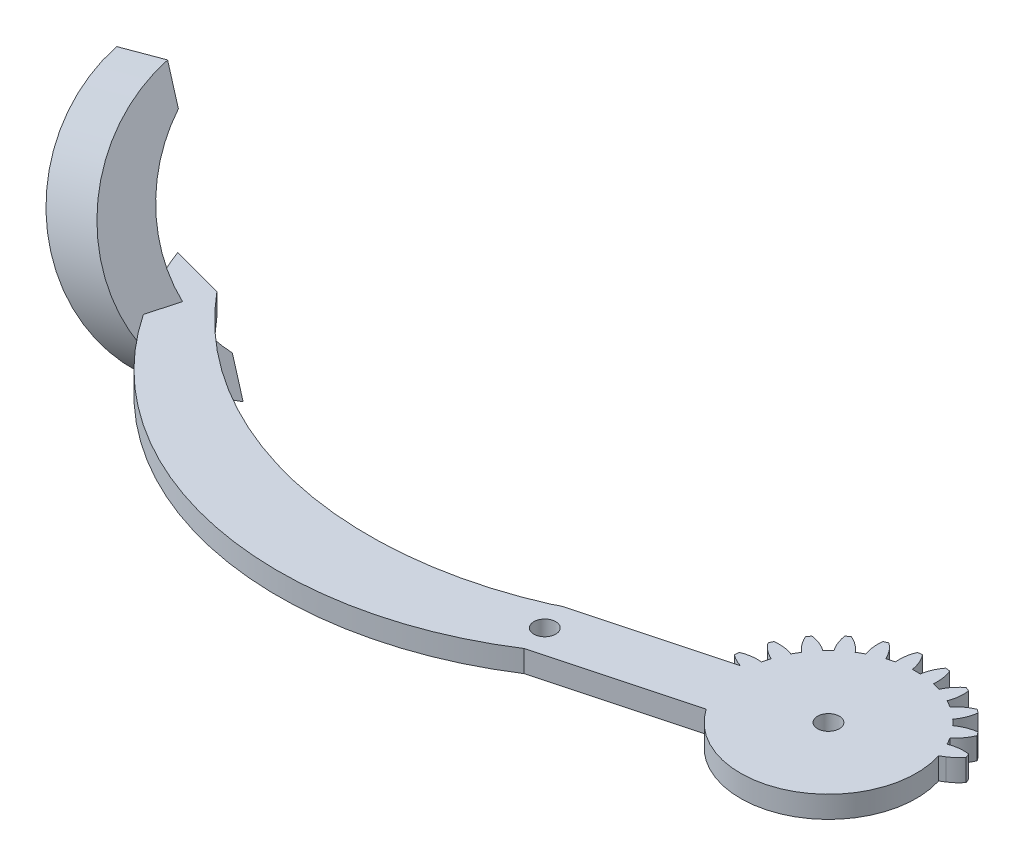
SolidWorks part; units mm, degrees
ref_plane "Front Plane" through (0, 0, 0) normal (0, 0, 1) x (1, 0, 0)
ref_plane "Top Plane" through (0, 0, 0) normal (0, 1, 0) x (1, 0, 0)
ref_plane "Right Plane" through (0, 0, 0) normal (1, 0, 0) x (0, 0, -1)
sketch "Sketch1" plane through (0, 0, 0) normal (0, 1, 0) x (1, 0, 0)
  line L0 (20.6437, 4) -> (2.0816, 4)
  line L1 (2.0816, -4) -> (20.6437, -4)
  arc A0 (2.0816, 4) -> (3.5217, 5.3071) centre (-0.7683, 8.5867) ccw
  arc A1 (3.5217, 5.3071) -> (3.2829, 5.8838) centre (-10.1063, 0) ccw
  arc A2 (3.2829, 5.8838) -> (0.6271, 5.5703) centre (2.5684, 0.5313) ccw
  arc A3 (0.6271, 5.5703) -> (0.0844, 6.5103) centre (-10.1063, 0) ccw
  arc A4 (0.0844, 6.5103) -> (1.6838, 8.6535) centre (-3.3089, 10.711) ccw
  arc A5 (1.6838, 8.6535) -> (1.3038, 9.1487) centre (-10.1063, 0) ccw
  arc A6 (1.3038, 9.1487) -> (-1.1803, 8.1585) centre (1.999, 3.7936) ccw
  arc A7 (-1.1803, 8.1585) -> (-1.9479, 8.926) centre (-10.1063, 0) ccw
  arc A8 (-1.9479, 8.926) -> (-0.9576, 11.4102) centre (-6.3127, 12.1053) ccw
  arc A9 (-0.9576, 11.4102) -> (-1.4528, 11.7901) centre (-10.1063, 0) ccw
  arc A10 (-1.4528, 11.7901) -> (-3.596, 10.1907) centre (0.6046, 6.7975) ccw
  arc A11 (-3.596, 10.1907) -> (-4.5361, 10.7334) centre (-10.1063, 0) ccw
  arc A12 (-4.5361, 10.7334) -> (-4.2225, 13.3892) centre (-9.5751, 12.6747) ccw
  arc A13 (-4.2225, 13.3892) -> (-4.7992, 13.6281) centre (-10.1063, 0) ccw
  arc A14 (-4.7992, 13.6281) -> (-6.4554, 11.5285) centre (-1.5196, 9.3381) ccw
  arc A15 (-6.4554, 11.5285) -> (-7.5039, 11.8094) centre (-10.1063, 0) ccw
  arc A16 (-7.5039, 11.8094) -> (-7.8884, 14.4558) centre (-12.8736, 12.3803) ccw
  arc A17 (-7.8884, 14.4558) -> (-8.5072, 14.5373) centre (-10.1063, 0) ccw
  arc A18 (-8.5072, 14.5373) -> (-9.5636, 12.0806) centre (-4.2291, 11.2423) ccw
  arc A19 (-9.5636, 12.0806) -> (-10.6491, 12.0806) centre (-10.1063, 0) ccw
  arc A20 (-10.6491, 12.0806) -> (-11.7054, 14.5373) centre (-15.9836, 11.2423) ccw
  arc A21 (-11.7054, 14.5373) -> (-12.3243, 14.4558) centre (-10.1063, 0) ccw
  arc A22 (-12.3243, 14.4558) -> (-12.7088, 11.8094) centre (-7.3391, 12.3803) ccw
  arc A23 (-12.7088, 11.8094) -> (-13.7573, 11.5285) centre (-10.1063, 0) ccw
  arc A24 (-13.7573, 11.5285) -> (-15.4135, 13.6281) centre (-18.6931, 9.3381) ccw
  arc A25 (-15.4135, 13.6281) -> (-15.9901, 13.3892) centre (-10.1063, 0) ccw
  arc A26 (-15.9901, 13.3892) -> (-15.6766, 10.7334) centre (-10.6376, 12.6747) ccw
  arc A27 (-15.6766, 10.7334) -> (-16.6166, 10.1907) centre (-10.1063, 0) ccw
  arc A28 (-16.6166, 10.1907) -> (-18.7599, 11.7901) centre (-20.8173, 6.7975) ccw
  arc A29 (-18.7599, 11.7901) -> (-19.255, 11.4102) centre (-10.1063, 0) ccw
  arc A30 (-19.255, 11.4102) -> (-18.2648, 8.926) centre (-13.9, 12.1053) ccw
  arc A31 (-18.2648, 8.926) -> (-19.0324, 8.1585) centre (-10.1063, 0) ccw
  arc A32 (-19.0324, 8.1585) -> (-21.5165, 9.1487) centre (-22.2117, 3.7936) ccw
  arc A33 (-21.5165, 9.1487) -> (-21.8965, 8.6535) centre (-10.1063, 0) ccw
  arc A34 (-21.8965, 8.6535) -> (-20.2971, 6.5103) centre (-16.9038, 10.711) ccw
  arc A35 (-20.2971, 6.5103) -> (-20.8398, 5.5703) centre (-10.1063, 0) ccw
  arc A36 (-20.8398, 5.5703) -> (-23.4956, 5.8838) centre (-22.7811, 0.5313) ccw
  arc A37 (-23.4956, 5.8838) -> (-23.7344, 5.3071) centre (-10.1063, 0) ccw
  arc A38 (-23.7344, 5.3071) -> (-21.6348, 3.6509) centre (-19.4444, 8.5867) ccw
  arc A39 (-21.6348, 3.6509) -> (-21.9157, 2.6025) centre (-10.1063, 0) ccw
  arc A40 (-21.9157, 2.6025) -> (-24.5622, 2.2179) centre (-22.4867, -2.7673) ccw
  arc A41 (-24.5622, 2.2179) -> (-24.6437, 1.5991) centre (-10.1063, 0) ccw
  arc A42 (-24.6437, 1.5991) -> (-22.1869, 0.5427) centre (-21.3486, 5.8773) ccw
  arc A43 (-22.1869, 0.5427) -> (-22.1869, -0.5427) centre (-10.1063, 0) ccw
  arc A44 (-22.1869, -0.5427) -> (-24.6437, -1.5991) centre (-21.3486, -5.8773) ccw
  arc A45 (-24.6437, -1.5991) -> (-24.5622, -2.2179) centre (-10.1063, 0) ccw
  arc A46 (-24.5622, -2.2179) -> (-21.9157, -2.6025) centre (-22.4867, 2.7673) ccw
  arc A47 (-21.9157, -2.6025) -> (-21.6348, -3.6509) centre (-10.1063, 0) ccw
  arc A48 (-21.6348, -3.6509) -> (-23.7344, -5.3071) centre (-19.4444, -8.5867) ccw
  arc A49 (-23.7344, -5.3071) -> (-23.4956, -5.8838) centre (-10.1063, 0) ccw
  arc A50 (-23.4956, -5.8838) -> (-20.8398, -5.5703) centre (-22.7811, -0.5313) ccw
  arc A51 (-20.8398, -5.5703) -> (-20.2971, -6.5103) centre (-10.1063, 0) ccw
  arc A52 (-20.2971, -6.5103) -> (-21.8965, -8.6535) centre (-16.9038, -10.711) ccw
  arc A53 (-21.8965, -8.6535) -> (-21.5165, -9.1487) centre (-10.1063, 0) ccw
  arc A54 (-21.5165, -9.1487) -> (-19.0324, -8.1585) centre (-22.2117, -3.7936) ccw
  arc A55 (-19.0324, -8.1585) -> (-18.2648, -8.926) centre (-10.1063, 0) ccw
  arc A56 (-18.2648, -8.926) -> (-19.255, -11.4102) centre (-13.9, -12.1053) ccw
  arc A57 (-19.255, -11.4102) -> (-18.7599, -11.7901) centre (-10.1063, 0) ccw
  arc A58 (-18.7599, -11.7901) -> (-16.6166, -10.1907) centre (-20.8173, -6.7975) ccw
  arc A59 (-16.6166, -10.1907) -> (-15.6766, -10.7334) centre (-10.1063, 0) ccw
  arc A60 (-15.6766, -10.7334) -> (-15.9901, -13.3892) centre (-10.6376, -12.6747) ccw
  arc A61 (-15.9901, -13.3892) -> (-15.4135, -13.6281) centre (-10.1063, 0) ccw
  arc A62 (-15.4135, -13.6281) -> (-13.7573, -11.5285) centre (-18.6931, -9.3381) ccw
  arc A63 (-13.7573, -11.5285) -> (-12.7088, -11.8094) centre (-10.1063, 0) ccw
  arc A64 (-12.7088, -11.8094) -> (-12.3243, -14.4558) centre (-7.3391, -12.3803) ccw
  arc A65 (-12.3243, -14.4558) -> (-11.7054, -14.5373) centre (-10.1063, 0) ccw
  arc A66 (-11.7054, -14.5373) -> (-10.6491, -12.0806) centre (-15.9836, -11.2423) ccw
  arc A67 (-10.6491, -12.0806) -> (-9.5636, -12.0806) centre (-10.1063, 0) ccw
  arc A68 (-9.5636, -12.0806) -> (-8.5072, -14.5373) centre (-4.2291, -11.2423) ccw
  arc A69 (-8.5072, -14.5373) -> (-7.8884, -14.4558) centre (-10.1063, 0) ccw
  arc A70 (-7.8884, -14.4558) -> (-7.5039, -11.8094) centre (-12.8736, -12.3803) ccw
  arc A71 (-7.5039, -11.8094) -> (-6.4554, -11.5285) centre (-10.1063, 0) ccw
  arc A72 (-6.4554, -11.5285) -> (-4.7992, -13.6281) centre (-1.5196, -9.3381) ccw
  arc A73 (-4.7992, -13.6281) -> (-4.2225, -13.3892) centre (-10.1063, 0) ccw
  arc A74 (-4.2225, -13.3892) -> (-4.5361, -10.7334) centre (-9.5751, -12.6747) ccw
  arc A75 (-4.5361, -10.7334) -> (-3.596, -10.1907) centre (-10.1063, 0) ccw
  arc A76 (-3.596, -10.1907) -> (-1.4528, -11.7901) centre (0.6046, -6.7975) ccw
  arc A77 (-1.4528, -11.7901) -> (-0.9576, -11.4102) centre (-10.1063, 0) ccw
  arc A78 (-0.9576, -11.4102) -> (-1.9479, -8.926) centre (-6.3127, -12.1053) ccw
  arc A79 (-1.9479, -8.926) -> (-1.1803, -8.1585) centre (-10.1063, 0) ccw
  arc A80 (-1.1803, -8.1585) -> (1.3038, -9.1487) centre (1.999, -3.7936) ccw
  arc A81 (1.3038, -9.1487) -> (1.6838, -8.6535) centre (-10.1063, 0) ccw
  arc A82 (1.6838, -8.6535) -> (0.0844, -6.5103) centre (-3.3089, -10.711) ccw
  arc A83 (0.0844, -6.5103) -> (0.6271, -5.5703) centre (-10.1063, 0) ccw
  arc A84 (0.6271, -5.5703) -> (3.2829, -5.8838) centre (2.5684, -0.5313) ccw
  arc A85 (3.2829, -5.8838) -> (3.5217, -5.3071) centre (-10.1063, 0) ccw
  arc A86 (3.5217, -5.3071) -> (2.0816, -4) centre (-0.7683, -8.5867) ccw
  arc A87 (20.6437, -4) -> (20.6437, 4) centre (20.6437, 0) ccw
  circle A88 centre (-10.1063, 0) radius 1.5
  circle A89 centre (20.6437, 0) radius 1.5
  dimension "D1" = 3
  dimension "D2" = 3
extrude "Boss-Extrude1" add sketch "Sketch1" along normal blind 3
sketch "Sketch3" plane through (0, 3, 0) normal (0, 1, 0) x (1, 0, 0)
  line L0 (-10.1063, 0) -> (-40.8563, 0) construction
  line L1 (-10.1063, 0) -> (-40.8563, -8.2394)
  line L2 (-11.1416, 3.8637) -> (-41.8916, -4.3757)
  line L3 (-9.0711, -3.8637) -> (-39.8211, -12.1031)
  circle A0 centre (-10.1063, 0) radius 1.5
  circle A1 centre (20.6437, 0) radius 1.5 construction
  circle A2 centre (20.6437, 0) radius 1.5
  circle A3 centre (-40.8563, -8.2394) radius 1.5
  circle A4 centre (-40.8563, -8.2394) radius 4
  circle A5 centre (-10.1063, 0) radius 4
  dimension "D2" = 3
  dimension "D5" = 3
  dimension "D6" = 8
  dimension "D7" = 8
  dimension "D1" = 30.75
  dimension "D3" = 30.75
  dimension "D4" = 15
extrude "Boss-Extrude2" add sketch "Sketch3" against normal blind 3 contours L0 A5 L2 | A5 L0 L2 A4 L1 | A4 A3 | A5 L1 A4 L3 | L0 A0 L1 A5 | A0 L0 A5 L1 region at (-13.0123, 3, 0.3826) region at (-12.8563, 3, -0.1131) region at (-28.0097, 3, 2.8847) region at (-17.5095, 3, -1.168) region at (-24.9445, 3, 6.1234) region at (-37.0027, 3, 7.7321)
sketch "Sketch4" plane through (0, 3, 0) normal (0, 1, 0) x (1, 0, 0)
  line L0 (20.6437, 4) -> (2.0816, 4) construction
  line L1 (2.0816, -4) -> (20.6437, -4) construction
  line L2 (20.6437, 4) -> (2.0816, 4)
  line L3 (2.0816, -4) -> (20.6437, -4)
  line L4 (2.0816, 4) -> (1.4381, 3.6001)
  line L5 (-20.8438, -7.0182) -> (-20.0942, -6.8174)
  line L8 (-22.9143, 0.7092) -> (-41.8916, -4.3757)
  line L9 (-39.8211, -12.1031) -> (-20.8438, -7.0182)
  line L10 (2.0816, -4) -> (20.6437, -4)
  line L11 (20.6437, 4) -> (2.0816, 4)
  line L12 (-22.9143, 0.7092) -> (-41.8916, -4.3757)
  line L13 (-39.8211, -12.1031) -> (-20.8438, -7.0182)
  line L14 (2.0816, -4) -> (20.6437, -4)
  line L15 (20.6437, 4) -> (2.0816, 4)
  circle A0 centre (-10.1063, 0) radius 12.0927
  arc A1 (3.2829, 5.8838) -> (0.6271, 5.5703) centre (2.5684, 0.5313) ccw construction
  arc A2 (3.5217, 5.3071) -> (3.2829, 5.8838) centre (-10.1063, 0) ccw construction
  arc A3 (2.0816, 4) -> (3.5217, 5.3071) centre (-0.7683, 8.5867) ccw construction
  arc A4 (20.6437, -4) -> (20.6437, 4) centre (20.6437, 0) ccw construction
  arc A5 (3.5217, -5.3071) -> (2.0816, -4) centre (-0.7683, -8.5867) ccw construction
  arc A6 (3.2829, -5.8838) -> (3.5217, -5.3071) centre (-10.1063, 0) ccw construction
  arc A7 (0.6271, -5.5703) -> (3.2829, -5.8838) centre (2.5684, -0.5313) ccw construction
  arc A8 (3.2829, 5.8838) -> (0.6271, 5.5703) centre (2.5684, 0.5313) ccw
  arc A9 (3.5217, 5.3071) -> (3.2829, 5.8838) centre (-10.1063, 0) ccw
  arc A10 (2.0816, 4) -> (3.5217, 5.3071) centre (-0.7683, 8.5867) ccw
  arc A11 (20.6437, -4) -> (20.6437, 4) centre (20.6437, 0) ccw
  arc A12 (3.5217, -5.3071) -> (2.0816, -4) centre (-0.7683, -8.5867) ccw
  arc A13 (3.2829, -5.8838) -> (3.5217, -5.3071) centre (-10.1063, 0) ccw
  arc A14 (0.6271, -5.5703) -> (3.2829, -5.8838) centre (2.5684, -0.5313) ccw
  arc A95 (-24.6437, 1.5991) -> (-22.9143, 0.7092) centre (-21.3486, 5.8773) ccw
  arc A96 (-41.8916, -4.3757) -> (-39.8211, -12.1031) centre (-40.8563, -8.2394) ccw
  arc A97 (-20.8438, -7.0182) -> (-21.8965, -8.6535) centre (-16.9038, -10.711) ccw
  arc A98 (-21.8965, -8.6535) -> (-21.5165, -9.1487) centre (-10.1063, 0) ccw
  arc A99 (-21.5165, -9.1487) -> (-19.0324, -8.1585) centre (-22.2117, -3.7936) ccw
  arc A100 (-19.0324, -8.1585) -> (-18.2648, -8.926) centre (-10.1063, 0) ccw
  arc A101 (-18.2648, -8.926) -> (-19.255, -11.4102) centre (-13.9, -12.1053) ccw
  arc A102 (-19.255, -11.4102) -> (-18.7599, -11.7901) centre (-10.1063, 0) ccw
  arc A103 (-18.7599, -11.7901) -> (-16.6166, -10.1907) centre (-20.8173, -6.7975) ccw
  arc A104 (-16.6166, -10.1907) -> (-15.6766, -10.7334) centre (-10.1063, 0) ccw
  arc A105 (-15.6766, -10.7334) -> (-15.9901, -13.3892) centre (-10.6376, -12.6747) ccw
  arc A106 (-15.9901, -13.3892) -> (-15.4135, -13.6281) centre (-10.1063, 0) ccw
  arc A107 (-15.4135, -13.6281) -> (-13.7573, -11.5285) centre (-18.6931, -9.3381) ccw
  arc A108 (-13.7573, -11.5285) -> (-12.7088, -11.8094) centre (-10.1063, 0) ccw
  arc A109 (-12.7088, -11.8094) -> (-12.3243, -14.4558) centre (-7.3391, -12.3803) ccw
  arc A110 (-12.3243, -14.4558) -> (-11.7054, -14.5373) centre (-10.1063, 0) ccw
  arc A111 (-11.7054, -14.5373) -> (-10.6491, -12.0806) centre (-15.9836, -11.2423) ccw
  arc A112 (-10.6491, -12.0806) -> (-9.5636, -12.0806) centre (-10.1063, 0) ccw
  arc A113 (-9.5636, -12.0806) -> (-8.5072, -14.5373) centre (-4.2291, -11.2423) ccw
  arc A114 (-8.5072, -14.5373) -> (-7.8884, -14.4558) centre (-10.1063, 0) ccw
  arc A115 (-7.8884, -14.4558) -> (-7.5039, -11.8094) centre (-12.8736, -12.3803) ccw
  arc A116 (-7.5039, -11.8094) -> (-6.4554, -11.5285) centre (-10.1063, 0) ccw
  arc A117 (-6.4554, -11.5285) -> (-4.7992, -13.6281) centre (-1.5196, -9.3381) ccw
  arc A118 (-4.7992, -13.6281) -> (-4.2225, -13.3892) centre (-10.1063, 0) ccw
  arc A119 (-4.2225, -13.3892) -> (-4.5361, -10.7334) centre (-9.5751, -12.6747) ccw
  arc A120 (-4.5361, -10.7334) -> (-3.596, -10.1907) centre (-10.1063, 0) ccw
  arc A121 (-3.596, -10.1907) -> (-1.4528, -11.7901) centre (0.6046, -6.7975) ccw
  arc A122 (-1.4528, -11.7901) -> (-0.9576, -11.4102) centre (-10.1063, 0) ccw
  arc A123 (-0.9576, -11.4102) -> (-1.9479, -8.926) centre (-6.3127, -12.1053) ccw
  arc A124 (-1.9479, -8.926) -> (-1.1803, -8.1585) centre (-10.1063, 0) ccw
  arc A125 (-1.1803, -8.1585) -> (1.3038, -9.1487) centre (1.999, -3.7936) ccw
  arc A126 (1.3038, -9.1487) -> (1.6838, -8.6535) centre (-10.1063, 0) ccw
  arc A127 (1.6838, -8.6535) -> (0.0844, -6.5103) centre (-3.3089, -10.711) ccw
  arc A128 (0.0844, -6.5103) -> (0.6271, -5.5703) centre (-10.1063, 0) ccw
  arc A129 (0.6271, -5.5703) -> (3.2829, -5.8838) centre (2.5684, -0.5313) ccw
  arc A130 (3.2829, -5.8838) -> (3.5217, -5.3071) centre (-10.1063, 0) ccw
  arc A131 (3.5217, -5.3071) -> (2.0816, -4) centre (-0.7683, -8.5867) ccw
  arc A132 (20.6437, -4) -> (20.6437, 4) centre (20.6437, 0) ccw
  arc A133 (2.0816, 4) -> (3.5217, 5.3071) centre (-0.7683, 8.5867) ccw
  arc A134 (3.5217, 5.3071) -> (3.2829, 5.8838) centre (-10.1063, 0) ccw
  arc A135 (3.2829, 5.8838) -> (0.6271, 5.5703) centre (2.5684, 0.5313) ccw
  arc A136 (0.6271, 5.5703) -> (0.0844, 6.5103) centre (-10.1063, 0) ccw
  arc A137 (0.0844, 6.5103) -> (1.6838, 8.6535) centre (-3.3089, 10.711) ccw
  arc A138 (1.6838, 8.6535) -> (1.3038, 9.1487) centre (-10.1063, 0) ccw
  arc A139 (1.3038, 9.1487) -> (-1.1803, 8.1585) centre (1.999, 3.7936) ccw
  arc A140 (-1.1803, 8.1585) -> (-1.9479, 8.926) centre (-10.1063, 0) ccw
  arc A141 (-1.9479, 8.926) -> (-0.9576, 11.4102) centre (-6.3127, 12.1053) ccw
  arc A142 (-0.9576, 11.4102) -> (-1.4528, 11.7901) centre (-10.1063, 0) ccw
  arc A143 (-1.4528, 11.7901) -> (-3.596, 10.1907) centre (0.6046, 6.7975) ccw
  arc A144 (-3.596, 10.1907) -> (-4.5361, 10.7334) centre (-10.1063, 0) ccw
  arc A145 (-4.5361, 10.7334) -> (-4.2225, 13.3892) centre (-9.5751, 12.6747) ccw
  arc A146 (-4.2225, 13.3892) -> (-4.7992, 13.6281) centre (-10.1063, 0) ccw
  arc A147 (-4.7992, 13.6281) -> (-6.4554, 11.5285) centre (-1.5196, 9.3381) ccw
  arc A148 (-6.4554, 11.5285) -> (-7.5039, 11.8094) centre (-10.1063, 0) ccw
  arc A149 (-7.5039, 11.8094) -> (-7.8884, 14.4558) centre (-12.8736, 12.3803) ccw
  arc A150 (-7.8884, 14.4558) -> (-8.5072, 14.5373) centre (-10.1063, 0) ccw
  arc A151 (-8.5072, 14.5373) -> (-9.5636, 12.0806) centre (-4.2291, 11.2423) ccw
  arc A152 (-9.5636, 12.0806) -> (-10.6491, 12.0806) centre (-10.1063, 0) ccw
  arc A153 (-10.6491, 12.0806) -> (-11.7054, 14.5373) centre (-15.9836, 11.2423) ccw
  arc A154 (-11.7054, 14.5373) -> (-12.3243, 14.4558) centre (-10.1063, 0) ccw
  arc A155 (-12.3243, 14.4558) -> (-12.7088, 11.8094) centre (-7.3391, 12.3803) ccw
  arc A156 (-12.7088, 11.8094) -> (-13.7573, 11.5285) centre (-10.1063, 0) ccw
  arc A157 (-13.7573, 11.5285) -> (-15.4135, 13.6281) centre (-18.6931, 9.3381) ccw
  arc A158 (-15.4135, 13.6281) -> (-15.9901, 13.3892) centre (-10.1063, 0) ccw
  arc A159 (-15.9901, 13.3892) -> (-15.6766, 10.7334) centre (-10.6376, 12.6747) ccw
  arc A160 (-15.6766, 10.7334) -> (-16.6166, 10.1907) centre (-10.1063, 0) ccw
  arc A161 (-16.6166, 10.1907) -> (-18.7599, 11.7901) centre (-20.8173, 6.7975) ccw
  arc A162 (-18.7599, 11.7901) -> (-19.255, 11.4102) centre (-10.1063, 0) ccw
  arc A163 (-19.255, 11.4102) -> (-18.2648, 8.926) centre (-13.9, 12.1053) ccw
  arc A164 (-18.2648, 8.926) -> (-19.0324, 8.1585) centre (-10.1063, 0) ccw
  arc A165 (-19.0324, 8.1585) -> (-21.5165, 9.1487) centre (-22.2117, 3.7936) ccw
  arc A166 (-21.5165, 9.1487) -> (-21.8965, 8.6535) centre (-10.1063, 0) ccw
  arc A167 (-21.8965, 8.6535) -> (-20.2971, 6.5103) centre (-16.9038, 10.711) ccw
  arc A168 (-20.2971, 6.5103) -> (-20.8398, 5.5703) centre (-10.1063, 0) ccw
  arc A169 (-20.8398, 5.5703) -> (-23.4956, 5.8838) centre (-22.7811, 0.5313) ccw
  arc A170 (-23.4956, 5.8838) -> (-23.7344, 5.3071) centre (-10.1063, 0) ccw
  arc A171 (-23.7344, 5.3071) -> (-21.6348, 3.6509) centre (-19.4444, 8.5867) ccw
  arc A172 (-21.6348, 3.6509) -> (-21.9157, 2.6025) centre (-10.1063, 0) ccw
  arc A173 (-21.9157, 2.6025) -> (-24.5622, 2.2179) centre (-22.4867, -2.7673) ccw
  arc A174 (-24.5622, 2.2179) -> (-24.6437, 1.5991) centre (-10.1063, 0) ccw
  arc A175 (-24.6437, 1.5991) -> (-22.9143, 0.7092) centre (-21.3486, 5.8773) ccw
  arc A176 (-41.8916, -4.3757) -> (-39.8211, -12.1031) centre (-40.8563, -8.2394) ccw
  arc A177 (-20.8438, -7.0182) -> (-21.8965, -8.6535) centre (-16.9038, -10.711) ccw
  arc A178 (-21.8965, -8.6535) -> (-21.5165, -9.1487) centre (-10.1063, 0) ccw
  arc A179 (-21.5165, -9.1487) -> (-19.0324, -8.1585) centre (-22.2117, -3.7936) ccw
  arc A180 (-19.0324, -8.1585) -> (-18.2648, -8.926) centre (-10.1063, 0) ccw
  arc A181 (-18.2648, -8.926) -> (-19.255, -11.4102) centre (-13.9, -12.1053) ccw
  arc A182 (-19.255, -11.4102) -> (-18.7599, -11.7901) centre (-10.1063, 0) ccw
  arc A183 (-18.7599, -11.7901) -> (-16.6166, -10.1907) centre (-20.8173, -6.7975) ccw
  arc A184 (-16.6166, -10.1907) -> (-15.6766, -10.7334) centre (-10.1063, 0) ccw
  arc A185 (-15.6766, -10.7334) -> (-15.9901, -13.3892) centre (-10.6376, -12.6747) ccw
  arc A186 (-15.9901, -13.3892) -> (-15.4135, -13.6281) centre (-10.1063, 0) ccw
  arc A187 (-15.4135, -13.6281) -> (-13.7573, -11.5285) centre (-18.6931, -9.3381) ccw
  arc A188 (-13.7573, -11.5285) -> (-12.7088, -11.8094) centre (-10.1063, 0) ccw
  arc A189 (-12.7088, -11.8094) -> (-12.3243, -14.4558) centre (-7.3391, -12.3803) ccw
  arc A190 (-12.3243, -14.4558) -> (-11.7054, -14.5373) centre (-10.1063, 0) ccw
  arc A191 (-11.7054, -14.5373) -> (-10.6491, -12.0806) centre (-15.9836, -11.2423) ccw
  arc A192 (-10.6491, -12.0806) -> (-9.5636, -12.0806) centre (-10.1063, 0) ccw
  arc A193 (-9.5636, -12.0806) -> (-8.5072, -14.5373) centre (-4.2291, -11.2423) ccw
  arc A194 (-8.5072, -14.5373) -> (-7.8884, -14.4558) centre (-10.1063, 0) ccw
  arc A195 (-7.8884, -14.4558) -> (-7.5039, -11.8094) centre (-12.8736, -12.3803) ccw
  arc A196 (-7.5039, -11.8094) -> (-6.4554, -11.5285) centre (-10.1063, 0) ccw
  arc A197 (-6.4554, -11.5285) -> (-4.7992, -13.6281) centre (-1.5196, -9.3381) ccw
  arc A198 (-4.7992, -13.6281) -> (-4.2225, -13.3892) centre (-10.1063, 0) ccw
  arc A199 (-4.2225, -13.3892) -> (-4.5361, -10.7334) centre (-9.5751, -12.6747) ccw
  arc A200 (-4.5361, -10.7334) -> (-3.596, -10.1907) centre (-10.1063, 0) ccw
  arc A201 (-3.596, -10.1907) -> (-1.4528, -11.7901) centre (0.6046, -6.7975) ccw
  arc A202 (-1.4528, -11.7901) -> (-0.9576, -11.4102) centre (-10.1063, 0) ccw
  arc A203 (-0.9576, -11.4102) -> (-1.9479, -8.926) centre (-6.3127, -12.1053) ccw
  arc A204 (-1.9479, -8.926) -> (-1.1803, -8.1585) centre (-10.1063, 0) ccw
  arc A205 (-1.1803, -8.1585) -> (1.3038, -9.1487) centre (1.999, -3.7936) ccw
  arc A206 (1.3038, -9.1487) -> (1.6838, -8.6535) centre (-10.1063, 0) ccw
  arc A207 (1.6838, -8.6535) -> (0.0844, -6.5103) centre (-3.3089, -10.711) ccw
  arc A208 (0.0844, -6.5103) -> (0.6271, -5.5703) centre (-10.1063, 0) ccw
  arc A209 (0.6271, -5.5703) -> (3.2829, -5.8838) centre (2.5684, -0.5313) ccw
  arc A210 (3.2829, -5.8838) -> (3.5217, -5.3071) centre (-10.1063, 0) ccw
  arc A211 (3.5217, -5.3071) -> (2.0816, -4) centre (-0.7683, -8.5867) ccw
  arc A212 (20.6437, -4) -> (20.6437, 4) centre (20.6437, 0) ccw
  arc A213 (2.0816, 4) -> (3.5217, 5.3071) centre (-0.7683, 8.5867) ccw
  arc A214 (3.5217, 5.3071) -> (3.2829, 5.8838) centre (-10.1063, 0) ccw
  arc A215 (3.2829, 5.8838) -> (0.6271, 5.5703) centre (2.5684, 0.5313) ccw
  arc A216 (0.6271, 5.5703) -> (0.0844, 6.5103) centre (-10.1063, 0) ccw
  arc A217 (0.0844, 6.5103) -> (1.6838, 8.6535) centre (-3.3089, 10.711) ccw
  arc A218 (1.6838, 8.6535) -> (1.3038, 9.1487) centre (-10.1063, 0) ccw
  arc A219 (1.3038, 9.1487) -> (-1.1803, 8.1585) centre (1.999, 3.7936) ccw
  arc A220 (-1.1803, 8.1585) -> (-1.9479, 8.926) centre (-10.1063, 0) ccw
  arc A221 (-1.9479, 8.926) -> (-0.9576, 11.4102) centre (-6.3127, 12.1053) ccw
  arc A222 (-0.9576, 11.4102) -> (-1.4528, 11.7901) centre (-10.1063, 0) ccw
  arc A223 (-1.4528, 11.7901) -> (-3.596, 10.1907) centre (0.6046, 6.7975) ccw
  arc A224 (-3.596, 10.1907) -> (-4.5361, 10.7334) centre (-10.1063, 0) ccw
  arc A225 (-4.5361, 10.7334) -> (-4.2225, 13.3892) centre (-9.5751, 12.6747) ccw
  arc A226 (-4.2225, 13.3892) -> (-4.7992, 13.6281) centre (-10.1063, 0) ccw
  arc A227 (-4.7992, 13.6281) -> (-6.4554, 11.5285) centre (-1.5196, 9.3381) ccw
  arc A228 (-6.4554, 11.5285) -> (-7.5039, 11.8094) centre (-10.1063, 0) ccw
  arc A229 (-7.5039, 11.8094) -> (-7.8884, 14.4558) centre (-12.8736, 12.3803) ccw
  arc A230 (-7.8884, 14.4558) -> (-8.5072, 14.5373) centre (-10.1063, 0) ccw
  arc A231 (-8.5072, 14.5373) -> (-9.5636, 12.0806) centre (-4.2291, 11.2423) ccw
  arc A232 (-9.5636, 12.0806) -> (-10.6491, 12.0806) centre (-10.1063, 0) ccw
  arc A233 (-10.6491, 12.0806) -> (-11.7054, 14.5373) centre (-15.9836, 11.2423) ccw
  arc A234 (-11.7054, 14.5373) -> (-12.3243, 14.4558) centre (-10.1063, 0) ccw
  arc A235 (-12.3243, 14.4558) -> (-12.7088, 11.8094) centre (-7.3391, 12.3803) ccw
  arc A236 (-12.7088, 11.8094) -> (-13.7573, 11.5285) centre (-10.1063, 0) ccw
  arc A237 (-13.7573, 11.5285) -> (-15.4135, 13.6281) centre (-18.6931, 9.3381) ccw
  arc A238 (-15.4135, 13.6281) -> (-15.9901, 13.3892) centre (-10.1063, 0) ccw
  arc A239 (-15.9901, 13.3892) -> (-15.6766, 10.7334) centre (-10.6376, 12.6747) ccw
  arc A240 (-15.6766, 10.7334) -> (-16.6166, 10.1907) centre (-10.1063, 0) ccw
  arc A241 (-16.6166, 10.1907) -> (-18.7599, 11.7901) centre (-20.8173, 6.7975) ccw
  arc A242 (-18.7599, 11.7901) -> (-19.255, 11.4102) centre (-10.1063, 0) ccw
  arc A243 (-19.255, 11.4102) -> (-18.2648, 8.926) centre (-13.9, 12.1053) ccw
  arc A244 (-18.2648, 8.926) -> (-19.0324, 8.1585) centre (-10.1063, 0) ccw
  arc A245 (-19.0324, 8.1585) -> (-21.5165, 9.1487) centre (-22.2117, 3.7936) ccw
  arc A246 (-21.5165, 9.1487) -> (-21.8965, 8.6535) centre (-10.1063, 0) ccw
  arc A247 (-21.8965, 8.6535) -> (-20.2971, 6.5103) centre (-16.9038, 10.711) ccw
  arc A248 (-20.2971, 6.5103) -> (-20.8398, 5.5703) centre (-10.1063, 0) ccw
  arc A249 (-20.8398, 5.5703) -> (-23.4956, 5.8838) centre (-22.7811, 0.5313) ccw
  arc A250 (-23.4956, 5.8838) -> (-23.7344, 5.3071) centre (-10.1063, 0) ccw
  arc A251 (-23.7344, 5.3071) -> (-21.6348, 3.6509) centre (-19.4444, 8.5867) ccw
  arc A252 (-21.6348, 3.6509) -> (-21.9157, 2.6025) centre (-10.1063, 0) ccw
  arc A253 (-21.9157, 2.6025) -> (-24.5622, 2.2179) centre (-22.4867, -2.7673) ccw
  arc A254 (-24.5622, 2.2179) -> (-24.6437, 1.5991) centre (-10.1063, 0) ccw
  dimension "D2" = 24.1855
  dimension "D1" = 0
extrude "Cut-Extrude1" cut sketch "Sketch4" against normal blind 3 contours A178 A179 A0 L5 A177 | A182 A183 A0 A181 | A186 A187 A0 A185 | A190 A191 A0 A189 | A194 A195 A0 A193 | A198 A199 A0 A197 | A202 A203 A0 A201 | A206 A207 A0 A205 | A0 A14 A13 A12 L3 A11 L2 L4 region at (12.5694, 3, 0.1127) region at (0.3325, 3, 8.01) region at (-2.0963, 3, 10.4389) region at (-5.071, 3, 12.1563) region at (-8.3889, 3, 13.0454) region at (-11.8238, 3, 13.0454) region at (-15.1417, 3, 12.1563) region at (-18.1164, 3, 10.4389) region at (-20.5498, 3, 8.0549)
sketch "Sketch5" plane through (0, 0, 0) normal (0, -1, 0) x (-1, 0, 0)
  line L0 (110.7936, 11.2465) -> (103.4162, 9.24)
  arc A0 (39.8211, -12.1031) -> (110.7936, 11.2465) centre (65.8966, 28.1761) ccw
  arc A1 (41.8916, -4.3757) -> (103.4162, 9.24) centre (63.9062, 41.9599) ccw
  arc A2 (39.8211, -12.1031) -> (41.8916, -4.3757) centre (40.8563, -8.2394) ccw
  arc M6 (39.8211, -12.1031) -> (41.8916, -4.3757) centre (40.8563, -8.2394) ccw
  dimension "D1" = 51.2995
  dimension "D2" = 47.9829
extrude "Boss-Extrude3" add sketch "Sketch5" against normal blind 3 contours A1 A0 L0 M6 region at (-76.532, 0, 9.2176)
ref_plane "Plane1" through (-110.7936, 3, -11.2465) normal (0, -1, 0) x (-1, 0, 0)
sketch "Sketch11" plane through (-102.629, -48.4628, -28.1636) normal (-0.8776, -0.4144, -0.2408) x (-0.2178, -0.1028, 0.9706)
  line L0 (9.1328, 82.1852) -> (14.5114, 32.4754) construction
  line L1 (14.1812, 35.5274) -> (13.6433, 40.4984)
  line L2 (10.954, 65.3534) -> (10.4162, 70.3243)
  line L3 (666.0769, 153.3368) -> (-693.985, 6.1782) construction
  arc A0 (14.1812, 35.5274) -> (10.4162, 70.3243) centre (4.9423, 52.1299) ccw
  arc A1 (13.6433, 40.4984) -> (10.954, 65.3534) centre (-0.578, 51.5326) ccw
  dimension "D5" = 19
  dimension "D6" = 18
  dimension "D1" = 12
  dimension "D2" = 17
  dimension "D3" = 42
  dimension "D4" = 47
extrude "Boss-Extrude6" add sketch "Sketch11" along normal blind 11 from offset 25 offset against normal yes
